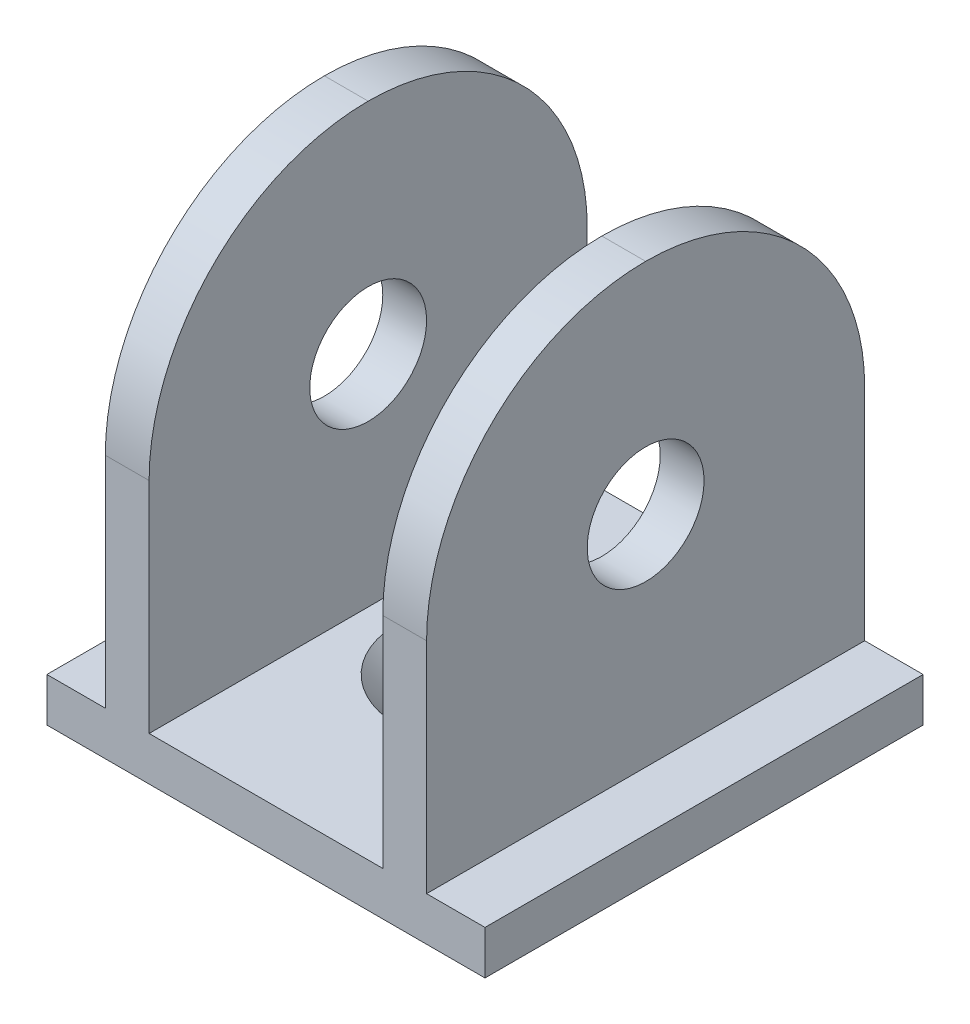
SolidWorks part; units mm, degrees
ref_plane "Alzado" through (0, 0, 0) normal (0, 0, 1) x (1, 0, 0)
ref_plane "Planta" through (0, 0, 0) normal (0, 1, 0) x (1, 0, 0)
ref_plane "Vista lateral" through (0, 0, 0) normal (1, 0, 0) x (0, 0, -1)
sketch "Croquis1" plane through (0, 0, 0) normal (0, 1, 0) x (1, 0, 0)
  line L1 (15, -15) -> (-15, -15)
  line L2 (15, -15) -> (15, 15)
  line L3 (15, 15) -> (-15, 15)
  line L4 (-15, -15) -> (-15, 15)
  line L5 (15, -15) -> (-15, 15) construction
  line L6 (15, 15) -> (-15, -15) construction
  point P0 (0, 0)
  dimension "D1" = 30
  dimension "D2" = 30
extrude "Saliente-Extruir1" add sketch "Croquis1" along normal blind 3
sketch "Croquis2" plane through (0, 3, 0) normal (0, 1, 0) x (1, 0, 0)
  line L0 (15, 15) -> (-15, 15) construction
  line L1 (-11, 15) -> (-8, 15)
  line L2 (-11, 15) -> (-11, -15)
  line L3 (-11, -15) -> (-8, -15)
  line L4 (-8, 15) -> (-8, -15)
  line L5 (-15, -15) -> (15, -15) construction
  line L6 (-15, 8.9544) -> (-11, 8.9544) construction
  line L7 (11, 15) -> (8, 15)
  line L8 (11, 15) -> (11, -15)
  line L9 (11, -15) -> (8, -15)
  line L10 (8, 15) -> (8, -15)
  line L11 (-15, 15) -> (-15, -15) construction
  line L12 (11, -11.3045) -> (15, -11.3045) construction
  line L13 (15, -15) -> (15, 15) construction
  dimension "D1" = 3
  dimension "D2" = 3
  dimension "D3" = 4
extrude "Saliente-Extruir2" add sketch "Croquis2" along normal blind 30
fillet "Redondeo1" radius 15 4 edges at (-9.5, 33, -15) (9.5, 33, -15) (9.5, 33, 15) (-9.5, 33, 15)
sketch "Croquis3" plane through (11, 0, 0) normal (1, 0, 0) x (0, 0, -1)
  circle A0 centre (0, 18) radius 4
  dimension "D1" = 8
extrude "Cortar-Extruir1" cut sketch "Croquis3" against normal through all
sketch "Croquis4" plane through (0, 3, 0) normal (0, 1, 0) x (1, 0, 0)
  circle A0 centre (0, 0) radius 3
  dimension "D1" = 6
extrude "Cortar-Extruir2" cut sketch "Croquis4" against normal through all
chamfer "Chaflán1" distance 3 angle 45 1 edges at (0, 3, 3)
